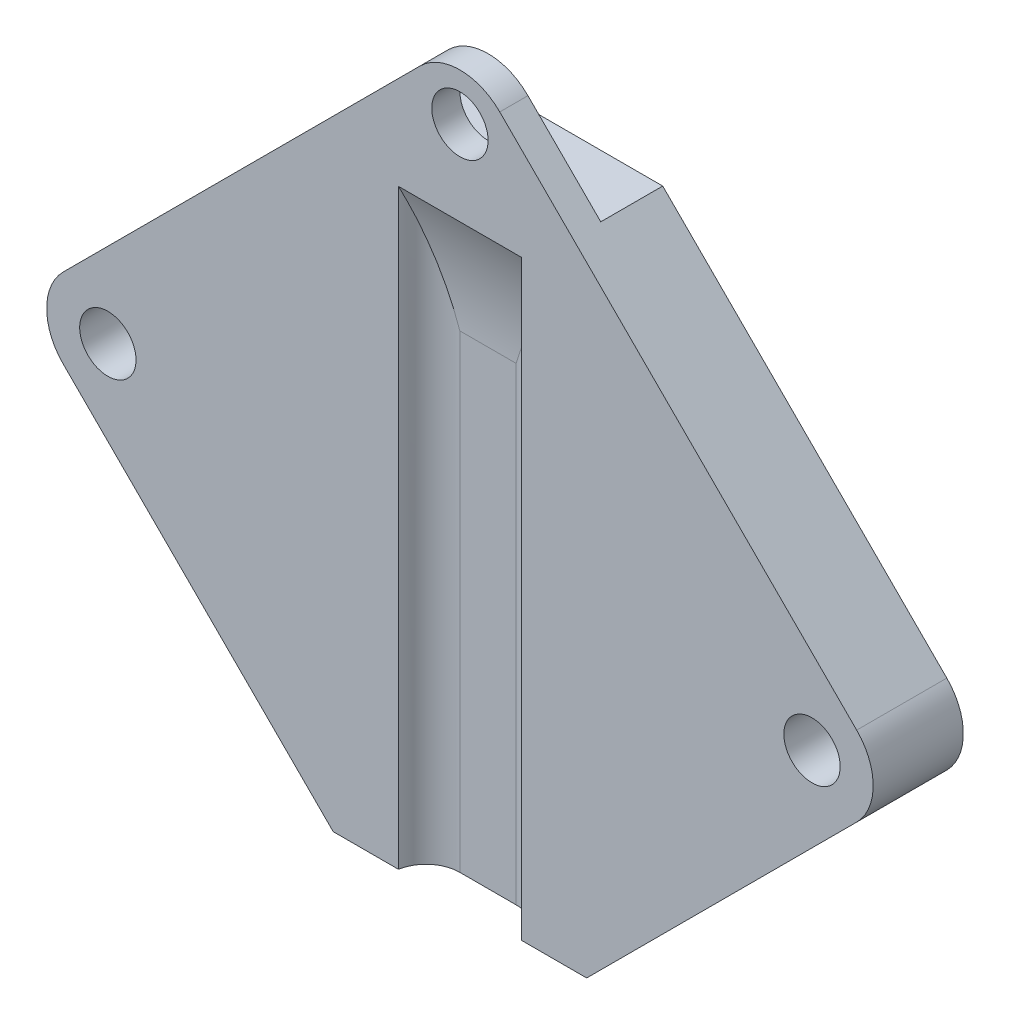
SolidWorks part; units mm, degrees
ref_plane "Front Plane" through (0, 0, 0) normal (0, 0, 1) x (1, 0, 0)
ref_plane "Top Plane" through (0, 0, 0) normal (0, 1, 0) x (1, 0, 0)
ref_plane "Right Plane" through (0, 0, 0) normal (1, 0, 0) x (0, 0, -1)
sketch3d "3DSketch5"
  line L5 (-13.5378, -2.6616, 36.9357) -> (-3.952, -12.2474, 36.9357)
  line L6 (-3.952, -12.2474, 36.9357) -> (5.048, -12.2474, 36.9357)
  line L7 (5.048, -12.2474, 36.9357) -> (14.6338, -2.6616, 36.9357)
  line L8 (14.6338, 0.1668, 36.9357) -> (1.9622, 12.8384, 36.9357)
  line L9 (-0.8662, 12.8384, 36.9357) -> (-13.5378, 0.1668, 36.9357)
  line L10 (-13.5378, -2.6616, 36.9357) -> (-3.952, -12.2474, 36.9357)
  line L11 (-3.952, -12.2474, 36.9357) -> (5.048, -12.2474, 36.9357)
  line L12 (5.048, -12.2474, 36.9357) -> (14.6338, -2.6616, 36.9357)
  line L13 (14.6338, 0.1668, 36.9357) -> (1.9622, 12.8384, 36.9357)
  line L14 (-0.8662, 12.8384, 36.9357) -> (-13.5378, 0.1668, 36.9357)
  circle A1 centre (0.548, 11.7526, 36.9357) radius 1
  circle A2 centre (0.548, 11.7526, 36.9357) radius 1
  circle A3 centre (13.048, -1.2474, 36.9357) radius 1
  circle A4 centre (13.048, -1.2474, 36.9357) radius 1
  circle A5 centre (-11.952, -1.2474, 36.9357) radius 1
  circle A6 centre (-11.952, -1.2474, 36.9357) radius 1
  arc A9 (14.6338, -2.6616, 36.9357) -> (14.6338, 0.1668, 36.9357) centre (13.2196, -1.2474, 36.9357) ccw
  arc A10 (1.9622, 12.8384, 36.9357) -> (-0.8662, 12.8384, 36.9357) centre (0.548, 11.4241, 36.9357) ccw
  arc A11 (-13.5378, 0.1668, 36.9357) -> (-13.5378, -2.6616, 36.9357) centre (-12.1235, -1.2474, 36.9357) ccw
  arc A12 (14.6338, -2.6616, 36.9357) -> (14.6338, 0.1668, 36.9357) centre (13.2196, -1.2474, 36.9357) ccw
  arc A13 (1.9622, 12.8384, 36.9357) -> (-0.8662, 12.8384, 36.9357) centre (0.548, 11.4241, 36.9357) ccw
  arc A14 (-13.5378, 0.1668, 36.9357) -> (-13.5378, -2.6616, 36.9357) centre (-12.1235, -1.2474, 36.9357) ccw
  point P5 (0.548, 11.7526, 37.9357)
  point P7 (0.548, 11.7526, 37.9357)
  point P10 (13.048, -1.2474, 37.9357)
  point P12 (13.048, -1.2474, 37.9357)
  point P15 (-11.952, -1.2474, 37.9357)
  point P17 (-11.952, -1.2474, 37.9357)
  point P19 (13.2196, -1.2474, 38.9357)
  point P25 (0.548, 11.4241, 38.9357)
  point P31 (-12.1235, -1.2474, 38.9357)
  point P34 (13.2196, -1.2474, 38.9357)
  point P35 (0.548, 11.4241, 38.9357)
  point P37 (-12.1235, -1.2474, 38.9357)
  dimension "D1" = 0
  dimension "D2" = 0
  dimension "D3" = 0
  dimension "D4" = 0
sketch "Sketch1" plane through (0, 0, 0) normal (0, 0, 1) x (1, 0, 0)
  line L0 (-13.5378, -2.6616) -> (-3.952, -12.2474) construction
  line L1 (-3.952, -12.2474) -> (5.048, -12.2474) construction
  line L2 (5.048, -12.2474) -> (14.6338, -2.6616) construction
  line L3 (14.6338, 0.1668) -> (1.9622, 12.8384) construction
  line L4 (-0.8662, 12.8384) -> (-13.5378, 0.1668) construction
  line L5 (-13.5378, -2.6616) -> (-3.952, -12.2474)
  line L6 (-3.952, -12.2474) -> (5.048, -12.2474)
  line L7 (5.048, -12.2474) -> (14.6338, -2.6616)
  line L8 (14.6338, 0.1668) -> (1.9622, 12.8384)
  line L9 (-0.8662, 12.8384) -> (-13.5378, 0.1668)
  circle A0 centre (-11.952, -1.2474) radius 1 construction
  arc A1 (-13.5378, 0.1668) -> (-13.5378, -2.6616) centre (-12.1235, -1.2474) ccw construction
  circle A2 centre (13.048, -1.2474) radius 1 construction
  arc A3 (14.6338, -2.6616) -> (14.6338, 0.1668) centre (13.2196, -1.2474) ccw construction
  circle A4 centre (0.548, 11.7526) radius 1 construction
  arc A5 (1.9622, 12.8384) -> (-0.8662, 12.8384) centre (0.548, 11.4241) ccw construction
  circle A6 centre (-11.952, -1.2474) radius 1
  arc A7 (-13.5378, 0.1668) -> (-13.5378, -2.6616) centre (-12.1235, -1.2474) ccw
  circle A8 centre (13.048, -1.2474) radius 1
  arc A9 (14.6338, -2.6616) -> (14.6338, 0.1668) centre (13.2196, -1.2474) ccw
  circle A10 centre (0.548, 11.7526) radius 1
  arc A11 (1.9622, 12.8384) -> (-0.8662, 12.8384) centre (0.548, 11.4241) ccw
extrude "Boss-Extrude1" add sketch "Sketch1" along normal blind 3.2
sketch "Sketch2" plane through (0, -12.2474, 0) normal (0, -1, 0) x (1, 0, 0)
  line L0 (-0.452, 3.4039) -> (1.548, 3.4039) construction
  line L1 (-0.452, 4.6039) -> (1.548, 4.6039)
  line L2 (-0.452, 2.2039) -> (1.548, 2.2039)
  line L3 (0.548, 3.2) -> (0.548, 0) construction
  line L6 (-3.952, 3.2) -> (5.048, 3.2) construction
  line L7 (-3.952, 0) -> (5.048, 0) construction
  arc A0 (-0.452, 4.6039) -> (-0.452, 2.2039) centre (-0.452, 3.4039) ccw
  arc A1 (1.548, 2.2039) -> (1.548, 4.6039) centre (1.548, 3.4039) ccw
  point P2 (0.548, 3.4039)
  dimension "D1" = 2.4
  dimension "D2" = 2
  dimension "D3" = 0.2039
extrude "Cut-Extrude1" cut sketch "Sketch2" against normal blind 21
sketch "Sketch3" plane through (0, 0, 0) normal (0, 0, -1) x (-1, 0, 0)
  line L0 (-14.4141, -2.8814) -> (-14.2027, -3.2474)
  line L1 (-11.8933, 0.7526) -> (-14.2027, 0.7526)
  line L2 (-14.2027, 0.7526) -> (-14.4141, 0.3865)
  line L4 (-14.2027, -3.2474) -> (-11.8933, -3.2474)
  line L5 (-11.8933, -3.2474) -> (-10.7386, -1.2474)
  line L6 (-10.7386, -1.2474) -> (-11.8933, 0.7526)
  line L7 (10.7973, 0.7526) -> (9.6426, -1.2474)
  line L8 (9.6426, -1.2474) -> (10.7973, -3.2474)
  line L9 (10.7973, -3.2474) -> (12.952, -3.2474)
  line L12 (12.952, 0.7526) -> (10.7973, 0.7526)
  line L17 (13.5378, 0.1668) -> (0.8662, 12.8384)
  line L18 (-1.9622, 12.8384) -> (-14.6338, 0.1668)
  line L19 (-14.6338, -2.6616) -> (-5.048, -12.2474)
  line L20 (-5.048, -12.2474) -> (3.952, -12.2474)
  line L21 (3.952, -12.2474) -> (13.5378, -2.6616)
  line L22 (13.5378, 0.1668) -> (12.952, 0.7526)
  line L23 (-14.4141, 0.3865) -> (-14.6338, 0.1668)
  line L24 (-14.6338, -2.6616) -> (-14.4141, -2.8814)
  line L26 (12.952, -3.2474) -> (13.5378, -2.6616)
  line L27 (-15.3574, -1.2474) -> (-15.2012, -1.518) [skipped]
  line L28 (14.1052, -0.9769) -> (13.684, -0.2474) [skipped]
  line L29 (13.318, -2.8814) -> (13.684, -2.2474) [skipped]
  arc A0 (-13.048, -3.2474) -> (-13.048, 0.7526) centre (-13.048, -1.2474) ccw construction
  arc A1 (11.952, 0.7526) -> (13.684, -2.2474) centre (11.952, -1.2474) ccw construction
  arc A5 (13.5378, -2.6616) -> (13.5378, 0.1668) centre (12.1235, -1.2474) ccw
  arc A6 (0.8662, 12.8384) -> (-1.9622, 12.8384) centre (-0.548, 11.4241) ccw
  arc A7 (-14.6338, 0.1668) -> (-14.6338, -2.6616) centre (-13.2196, -1.2474) ccw
  arc A8 (13.5378, -2.6616) -> (13.5378, 0.1668) centre (12.1235, -1.2474) ccw
  arc A10 (-14.6338, 0.1668) -> (-14.6338, -2.6616) centre (-13.2196, -1.2474) ccw
  dimension "D1" = 4
  dimension "D2" = 0
sketch "Sketch4" plane through (0, 0, 3.2) normal (0, 0, 1) x (1, 0, 0)
  line L1 (-34.8154, 29.2371) -> (-33.274, 29.2371)
  line L2 (-34.8154, 29.2371) -> (-34.8154, 27.371)
  line L3 (-34.8154, 27.371) -> (-33.274, 27.371)
  line L4 (-33.274, 29.2371) -> (-33.274, 27.371)
  line L5 (24.8872, -27.6637) -> (-23.3365, -27.6637)
  line L6 (24.8872, -27.6637) -> (24.8872, 22.4035)
  line L7 (24.8872, 22.4035) -> (-23.3365, 22.4035)
  line L8 (-23.3365, -27.6637) -> (-23.3365, 22.4035)
fillet "Fillet1" radius 10 1 edges at (0.548, 8.7526, 2.2039)
sketch "Sketch5" plane through (0, 0, 0) normal (0, 0, -1) x (-1, 0, 0)
  line L0 (-4.548, 10.2526) -> (-0.548, 14.2526)
  line L1 (-14.6338, 0.1668) -> (-1.9622, 12.8384) construction
  line L2 (-0.548, 14.2526) -> (3.452, 10.2526)
  line L3 (0.8662, 12.8384) -> (13.5378, 0.1668) construction
  line L4 (-4.548, 10.2526) -> (3.452, 10.2526)
  dimension "D1" = 4
extrude "Cut-Extrude3" cut sketch "Sketch5" against normal offset from surface (2.2 mm away) 1 up to face at (0.548, -0.851, 3.2)
